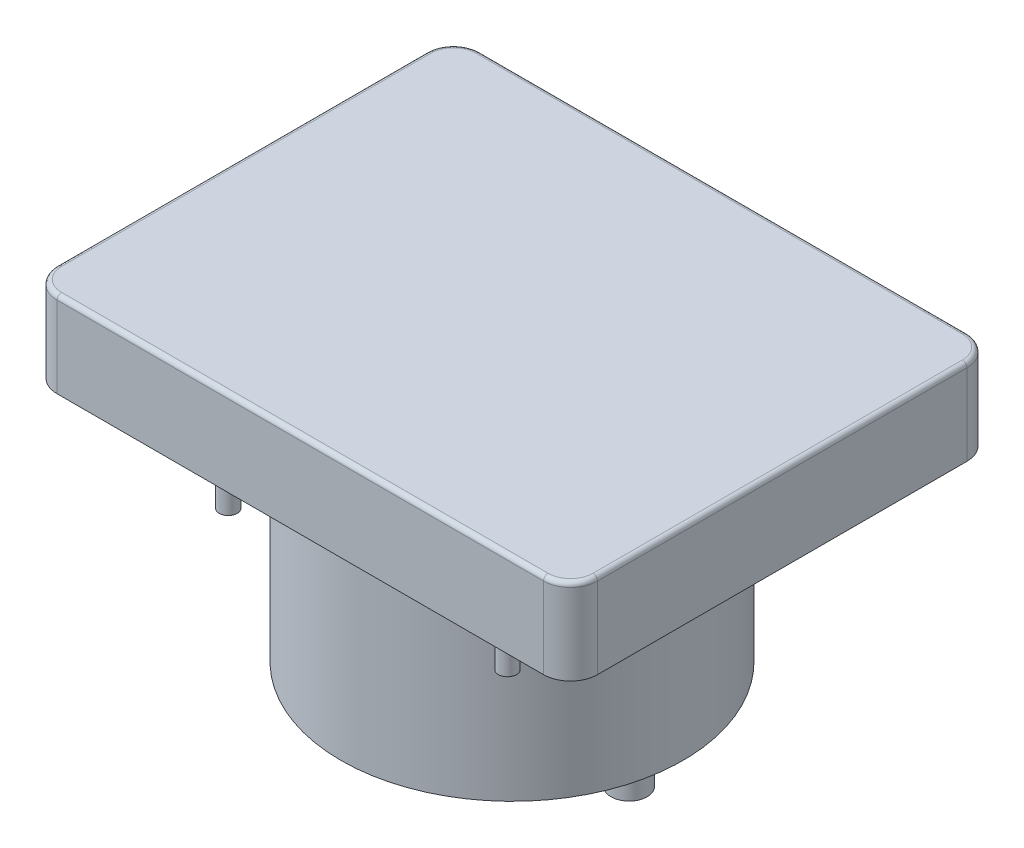
SolidWorks part; units mm, degrees
ref_plane "Front Plane" through (0, 0, 0) normal (0, 0, 1) x (1, 0, 0)
ref_plane "Top Plane" through (0, 0, 0) normal (0, 1, 0) x (1, 0, 0)
ref_plane "Right Plane" through (0, 0, 0) normal (1, 0, 0) x (0, 0, -1)
sketch "Sketch1" plane through (0, 0, 0) normal (0, 1, 0) x (1, 0, 0)
  line L0 (0, 0) -> (13, 0) construction
  line L1 (-30, -23.5) -> (30, -23.5)
  line L2 (-30, -23.5) -> (-30, 23.5)
  line L3 (-30, 23.5) -> (30, 23.5)
  line L4 (30, -23.5) -> (30, 23.5)
  line L5 (-30, -23.5) -> (30, 23.5) construction
  line L6 (-30, 23.5) -> (30, -23.5) construction
  line L7 (0, 0) -> (0, -8.5597) construction
  line L9 (-15.5, -16) -> (15.5, -16)
  line L10 (-15.5, -16) -> (-15.5, 16)
  line L11 (-15.5, 16) -> (15.5, 16)
  line L12 (15.5, -16) -> (15.5, 16)
  line L13 (-15.5, -16) -> (15.5, 16) construction
  line L14 (-15.5, 16) -> (15.5, -16) construction
  circle A0 centre (0, 0) radius 19
  circle A1 centre (13, 0) radius 2
  circle A2 centre (-13, 0) radius 2
  circle A3 centre (-15.5, 16) radius 1
  circle A4 centre (15.5, 16) radius 1
  circle A5 centre (15.5, -16) radius 1
  circle A6 centre (-15.5, -16) radius 1
  point P0 (0, 0)
  dimension "D3" = 38
  dimension "D7" = 2
  dimension "D8" = 4
  dimension "D1" = 60
  dimension "D2" = 47
  dimension "D4" = 26
  dimension "D5" = 31
  dimension "D6" = 32
extrude "Boss-Extrude1" add sketch "Sketch1" along normal blind 9.5 contours L3 L4 L1 L2
extrude "Boss-Extrude2" add sketch "Sketch1<3>" against normal blind 9 contours A4 | A5 | A6 | A3
sketch "Sketch1<3>" plane through (0, 0, 0) normal (0, 1, 0) x (1, 0, 0) same geometry as "Sketch1"
extrude "Boss-Extrude3" add sketch "Sketch1<4>" against normal blind 29.5 contours A1 | A2
sketch "Sketch1<4>" plane through (0, 0, 0) normal (0, 1, 0) x (1, 0, 0) same geometry as "Sketch1"
extrude "Boss-Extrude4" add sketch "Sketch1<5>" against normal blind 24 contours A0
sketch "Sketch1<5>" plane through (0, 0, 0) normal (0, 1, 0) x (1, 0, 0) same geometry as "Sketch1"
fillet "Fillet1" radius 3 4 edges at (-30, 4.75, 23.5) (30, 4.75, 23.5) (-30, 4.75, -23.5) (30, 4.75, -23.5)
fillet "Fillet2" radius 0.5 8 edges at (29.1213, 9.5, 22.6213) (0, 9.5, 23.5) (-29.1213, 9.5, 22.6213) (-30, 9.5, 0) (-29.1213, 9.5, -22.6213) (0, 9.5, -23.5) (29.1213, 9.5, -22.6213) (30, 9.5, 0)
